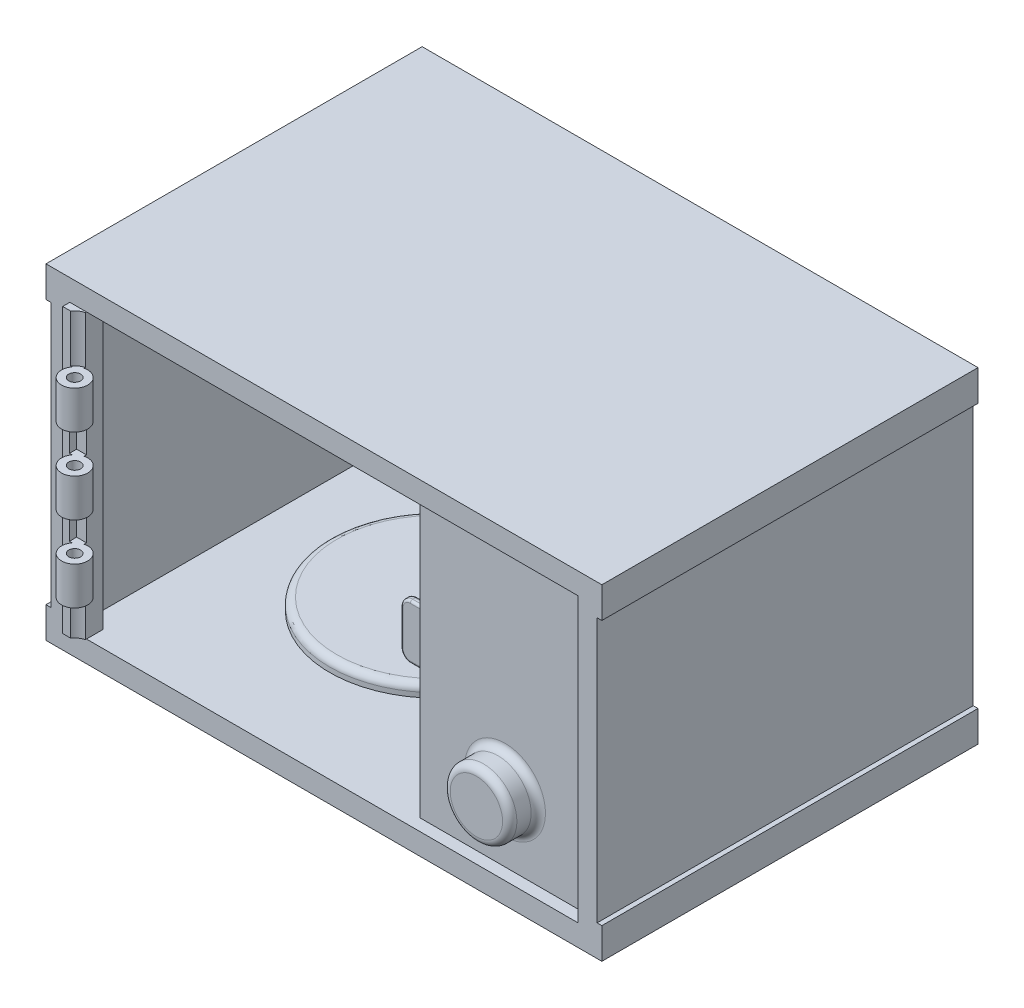
SolidWorks part; units mm, degrees
ref_plane "前视基准面" through (0, 0, 0) normal (0, 0, 1) x (1, 0, 0)
ref_plane "上视基准面" through (0, 0, 0) normal (0, 1, 0) x (1, 0, 0)
ref_plane "右视基准面" through (0, 0, 0) normal (1, 0, 0) x (0, 0, -1)
other "Configuration Table"
sketch "草图2" plane through (0, 0, 0) normal (0, 1, 0) x (1, 0, 0)
  line L1 (0, 0) -> (233.5, 0)
  line L2 (0, 0) -> (0, 158)
  line L3 (0, 158) -> (233.5, 158)
  line L4 (233.5, 0) -> (233.5, 158)
  dimension "D1" = 233.5
  dimension "D2" = 158
extrude "凸台-拉伸1" add sketch "草图2" along normal blind 9
sketch "草图4" plane through (0, 9, 0) normal (0, 1, 0) x (1, 0, 0)
  line L0 (0, 0) -> (233.5, 0) construction
  line L1 (0, 158) -> (10, 158)
  line L2 (0, 158) -> (0, 0)
  line L3 (0, 0) -> (10, 0)
  line L4 (10, 158) -> (10, 0)
  line L6 (223.5, 0) -> (233.5, 0)
  line L7 (223.5, 0) -> (223.5, 158)
  line L8 (223.5, 158) -> (233.5, 158)
  line L9 (233.5, 0) -> (233.5, 158)
  dimension "D1" = 10
  dimension "D2" = 10
extrude "凸台-拉伸2" add sketch "草图4" along normal blind 128
sketch "草图5" plane through (0, 9, 0) normal (0, 1, 0) x (1, 0, 0)
  line L0 (10, 0) -> (10, 158) construction
  line L1 (10, 149) -> (223.5, 149)
  line L2 (10, 149) -> (10, 146)
  line L3 (10, 146) -> (223.5, 146)
  line L4 (223.5, 149) -> (223.5, 146)
  line L5 (223.5, 158) -> (223.5, 0) construction
  line L6 (223.5, 158) -> (10, 158) construction
  dimension "D1" = 3
  dimension "D2" = 9
extrude "凸台-拉伸3" add sketch "草图5" along normal blind 128
sketch "草图6" plane through (0, 137, 0) normal (0, 1, 0) x (1, 0, 0)
  line L1 (0, 158) -> (233.5, 158)
  line L2 (0, 158) -> (0, 0)
  line L3 (0, 0) -> (233.5, 0)
  line L4 (233.5, 158) -> (233.5, 0)
extrude "凸台-拉伸4" add sketch "草图6" against normal blind 9
fillet "圆角1" radius 3 4 edges at (10, 68.5, -149) (116.75, 9, -149) (223.5, 68.5, -149) (116.75, 128, -149)
sketch "草图7" plane through (0, 0, 0) normal (-1, 0, 0) x (0, 0, 1)
  line L0 (-158, 137) -> (-158, 0) construction
  line L1 (-158, 124) -> (0, 124)
  line L2 (-158, 124) -> (-158, 13)
  line L3 (-158, 13) -> (0, 13)
  line L4 (0, 124) -> (0, 13)
  line L5 (0, 137) -> (0, 0) construction
  line L6 (-158, 137) -> (0, 137) construction
  line L7 (-158, 0) -> (0, 0) construction
  dimension "D1" = 13
  dimension "D2" = 13
extrude "切除-拉伸1" cut sketch "草图7" against normal blind 2
extrude "切除-拉伸2" cut sketch "草图7<2>" along normal blind 2 from surface starting at face at (233.5, 68.5, -79)
sketch "草图7<2>" plane through (0, 0, 0) normal (-1, 0, 0) x (0, 0, 1) same geometry as "草图7"
sketch "草图8" plane through (0, 9, 0) normal (0, 1, 0) x (1, 0, 0)
  line L1 (152, 146.3908) -> (155, 146.3908)
  line L2 (152, 146.3908) -> (152, 5)
  line L3 (152, 5) -> (155, 5)
  line L4 (155, 146.3908) -> (155, 5)
  line L5 (10, 0) -> (10, 146) construction
  line L7 (10, 0) -> (223.5, 0) construction
  dimension "D1" = 3
  dimension "D2" = 142
  dimension "D3" = 5
extrude "凸台-拉伸5" add sketch "草图8" along normal up to next
sketch "草图9" plane through (0, 0, 0) normal (0, 0, 1) x (1, 0, 0)
  line L1 (155, 128) -> (223.5, 128)
  line L2 (155, 128) -> (155, 9)
  line L3 (155, 9) -> (223.5, 9)
  line L4 (223.5, 128) -> (223.5, 9)
extrude "凸台-拉伸6" add sketch "草图9" against normal blind 5 from offset 5 offset against normal yes
sketch "草图11" plane through (0, 0, -5) normal (0, 0, 1) x (1, 0, 0)
  line L5 (223.5, 9) -> (223.5, 128) construction
  line L6 (10, 9) -> (223.5, 9) construction
  circle A0 centre (187.8, 37) radius 14
  dimension "D3" = 28
  dimension "D1" = 35.7
  dimension "D2" = 28
extrude "凸台-拉伸7" add sketch "草图11" along normal blind 12
sketch "草图12" plane through (0, 0, -5) normal (0, 0, 1) x (1, 0, 0)
  line L0 (152, 84.6577) -> (152, 56.3423)
  line L1 (152, 128) -> (152, 9) construction
  line L2 (149.0196, 82) -> (144.0196, 82)
  line L3 (140.0196, 78) -> (140.0196, 63)
  line L4 (144.0196, 59) -> (149.0196, 59)
  line L5 (10, 9) -> (223.5, 9) construction
  arc A0 (152, 84.6577) -> (149.0196, 82) centre (149.0196, 85) cw
  arc A1 (152, 56.3423) -> (149.0196, 59) centre (149.0196, 56) ccw
  arc A2 (144.0196, 82) -> (140.0196, 78) centre (144.0196, 78) ccw
  arc A3 (140.0196, 63) -> (144.0196, 59) centre (144.0196, 63) ccw
  dimension "D1" = 4
  dimension "D2" = 3
  dimension "D3" = 5
  dimension "D4" = 15
  dimension "D5" = 50
extrude "凸台-拉伸8" add sketch "草图12" against normal blind 3 from offset 4 offset against normal yes
sketch "草图13" plane through (0, 9, 0) normal (0, 1, 0) x (1, 0, 0)
  circle A0 centre (80.2882, 83.8864) radius 45
  dimension "D1" = 90
extrude "凸台-拉伸9" add sketch "草图13" along normal blind 5
fillet "圆角2" radius 3 3 edges at (201.8, 37, 7) (80.2882, 14, -38.8864) (173.8, 37, -5)
fillet "圆角3" radius 1 18 edges at (152, 70.5, -12) (152, 56.3423, -10.5) (152, 84.6577, -10.5) (151.0162, 58.2391, -12) (146.5196, 59, -12) (141.1912, 60.1716, -12) (140.0196, 70.5, -12) (141.1912, 80.8284, -12) (146.5196, 82, -12) (152, 70.5, -9) (151.0162, 58.2391, -9) (146.5196, 59, -9) (141.1912, 60.1716, -9) (140.0196, 70.5, -9) (141.1912, 80.8284, -9) (146.5196, 82, -9) (151.0162, 82.7609, -9) (151.0162, 82.7609, -12)
sketch "草图14" plane through (10, 0, 0) normal (1, 0, 0) x (0, 0, -1)
  line L0 (0, 128) -> (0, 9) construction
  line L1 (7, 128) -> (-3, 128)
  line L2 (7, 128) -> (7, 9)
  line L3 (7, 9) -> (-3, 9)
  line L4 (-3, 128) -> (-3, 9)
  dimension "D1" = 10
  dimension "D2" = 7
extrude "凸台-拉伸10" add sketch "草图14" along normal blind 7
sketch "草图15" plane through (0, 128, 0) normal (0, 1, 0) x (1, 0, 0)
  circle A0 centre (18.3679, -6.327) radius 5.5
  circle A1 centre (18.3679, -6.327) radius 2.5
  dimension "D1" = 5
  dimension "D2" = 11
extrude "凸台-拉伸11" add sketch "草图15" against normal blind 80 from offset 20 offset against normal yes
sketch "草图16" plane through (0, 0, 3) normal (0, 0, 1) x (1, 0, 0)
  line L0 (12.8679, 108) -> (12.8679, 28) construction
  line L1 (12.8679, 92) -> (23.8679, 92)
  line L2 (12.8679, 92) -> (12.8679, 76)
  line L3 (12.8679, 76) -> (23.8679, 76)
  line L4 (23.8679, 92) -> (23.8679, 76)
  line L5 (23.8679, 28) -> (23.8679, 108) construction
  line L6 (23.8679, 108) -> (12.8679, 108) construction
  line L7 (12.8679, 60) -> (23.8679, 60)
  line L8 (12.8679, 60) -> (12.8679, 44)
  line L9 (12.8679, 44) -> (23.8679, 44)
  line L10 (23.8679, 60) -> (23.8679, 44)
  dimension "D1" = 16
  dimension "D2" = 16
  dimension "D3" = 16
  dimension "D4" = 16
extrude "切除-拉伸4" cut sketch "草图16" against normal up to surface (3 mm away) and the other way blind 80 up to face at (83.5, 68.5, 0)
sketch "草图18" plane through (0, 128, 0) normal (0, 1, 0) x (1, 0, 0)
  line L0 (17, -3) -> (10, -3) construction
  line L1 (13.3747, -3) -> (17, -3)
  line L2 (17, -3) -> (17, -0.485)
  arc A0 (17, -0.485) -> (13.3747, -3) centre (18.3679, -6.327) ccw
  dimension "D1" = 6
extrude "切除-拉伸7" cut sketch "草图18" against normal up to surface (20 mm away) up to face at (18.3679, 108, 8.827)
extrude "切除-拉伸8" cut sketch "草图18<2>" along normal up to surface (-100 mm away) from surface up to face at (18.3679, 28, 8.827) starting at face at (13.5, 9, 1.5)
sketch "草图18<2>" plane through (0, 128, 0) normal (0, 1, 0) x (1, 0, 0) same geometry as "草图18"
